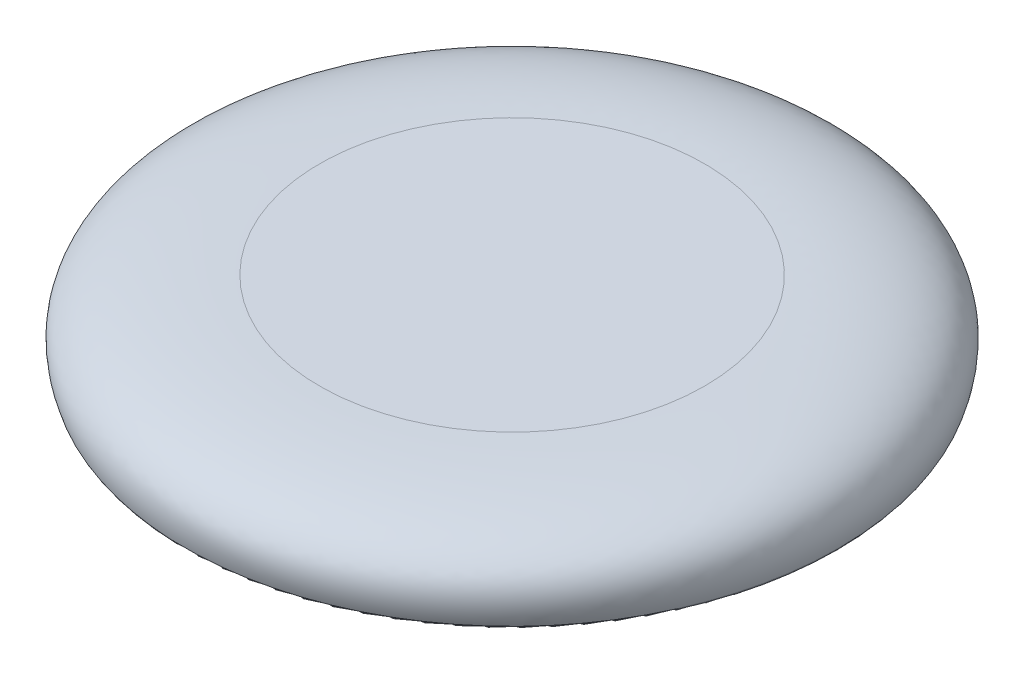
SolidWorks part; units mm, degrees
ref_plane "Front Plane" through (0, 0, 0) normal (0, 0, 1) x (1, 0, 0)
ref_plane "Top Plane" through (0, 0, 0) normal (0, 1, 0) x (1, 0, 0)
ref_plane "Right Plane" through (0, 0, 0) normal (1, 0, 0) x (0, 0, -1)
sketch "Sketch1" plane through (0, 0, 0) normal (0, 0, 1) x (1, 0, 0)
  line L1 (0, 32) -> (80, 32)
  line L3 (131, 0) -> (131.852, 16.2567)
  line L4 (131, 0) -> (135, 0)
  line L5 (0, 29) -> (80, 29)
  line L6 (0, 32) -> (0, 29)
  line L7 (0, 0) -> (0, 32) construction
  line L8 (137, 34.6801) -> (137, -28.1957) construction
  conic Q0 (80, 32) -> (135, 0) control (147.5, 32) rho 0.5
  spline S0 degree 1 poles (80, 29) (132.2056, 1.0916) knots 0 0 1 1 construction
  spline S1 degree 3 poles (80, 29) (80.6891, 29) (82.0769, 28.9948) (84.7752, 28.964) (88.0564, 28.8868) (91.83, 28.7327) (96.6483, 28.4456) (102.2677, 27.9344) (108.3611, 27.0808) (113.7984, 25.9923) (120.1638, 24.2404) (126.4441, 21.5153) (129.9403, 18.6716) (131.5643, 16.6883) (132.539, 15.2596) (133.4409, 13.2652) (133.9723, 10.6401) (133.9768, 8.2941) (133.7079, 6.243) (133.3643, 4.6176) (132.9545, 3.1882) (132.5531, 2.007) (132.3234, 1.3931) (132.2056, 1.0916) knots 0 0 0 0 0.015625 0.03125 0.0625 0.09375 0.125 0.1875 0.25 0.3125 0.375 0.5 0.625 0.647011 0.678261 0.75 0.8125 0.875 0.90625 0.9375 0.96875 0.984375 1 1 1 1 only from (80, 29) to (131.852, 16.2567)
  dimension "D5" = 67.5
  dimension "D1" = 80
  dimension "D2" = 135
  dimension "D3" = 32
  dimension "D6" = 4
  dimension "D8" = 87
  dimension "D9" = 137
  dimension "D7" = 3
revolve "Revolve1" add sketch "Sketch1" angle 360 about L7
fillet "Fillet1" radius 2 2 edges at (131, 0, 0) (135, 0, 0)
